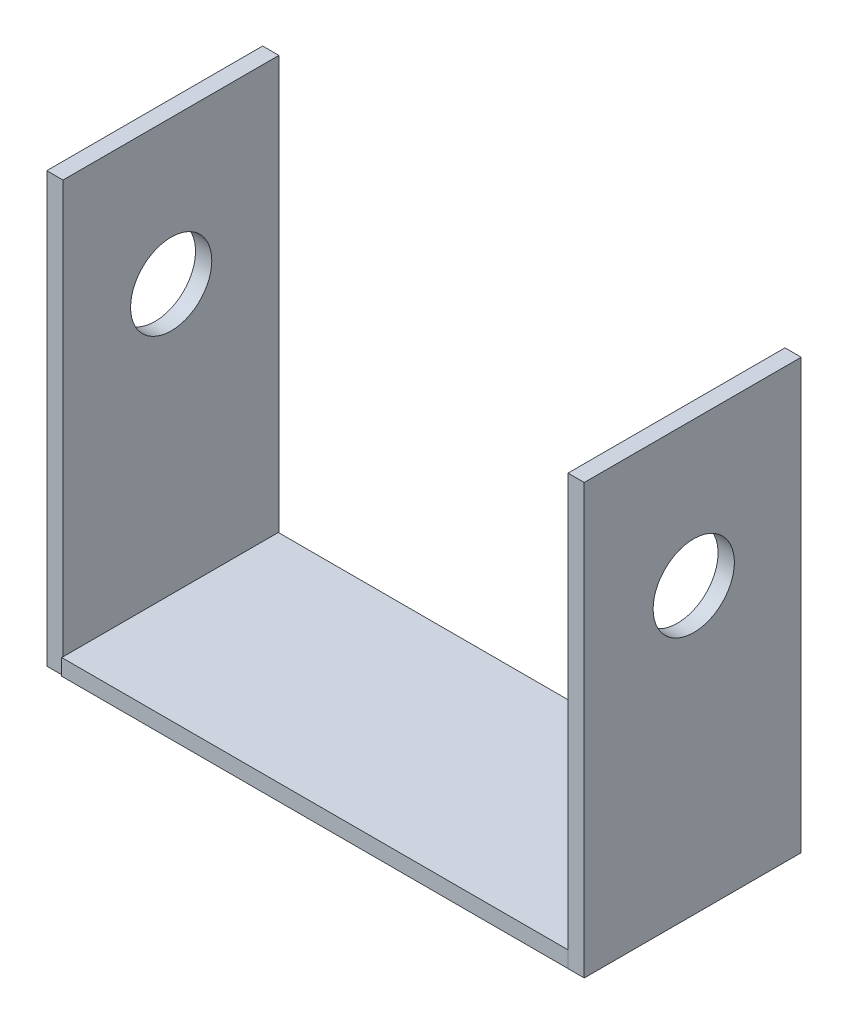
SolidWorks part; units mm, degrees
ref_plane "Front Plane" through (0, 0, 0) normal (0, 0, 1) x (1, 0, 0)
ref_plane "Top Plane" through (0, 0, 0) normal (0, 1, 0) x (1, 0, 0)
ref_plane "Right Plane" through (0, 0, 0) normal (1, 0, 0) x (0, 0, -1)
sketch "Sketch1" plane through (0, 0, 0) normal (0, 1, 0) x (1, 0, 0)
  line L1 (-23.7617, -10.16) -> (23.7617, -10.16)
  line L2 (-23.7617, -10.16) -> (-23.7617, 10.16)
  line L3 (-23.7617, 10.16) -> (23.7617, 10.16)
  line L4 (23.7617, -10.16) -> (23.7617, 10.16)
  line L5 (-23.7617, -10.16) -> (23.7617, 10.16) construction
  line L6 (-23.7617, 10.16) -> (23.7617, -10.16) construction
  point P0 (0, 0)
  dimension "D1" = 20.32
  dimension "D2" = 47.5234
extrude "Boss-Extrude1" add sketch "Sketch1" along normal blind 1.524
ref_plane "Plane1" through (-23.749, 0, 0) normal (1, 0, 0) x (0, 0, -1)
sketch "Sketch2" plane through (-23.749, 0, 0) normal (1, 0, 0) x (0, 0, -1)
  line L0 (10.2149, 0) -> (-10.0391, 0)
  line L1 (10.2149, 0) -> (10.2149, 40.259)
  line L2 (-10.0391, 0) -> (-10.0391, 40.259)
  line L3 (10.2149, 40.259) -> (-10.0391, 40.259)
  dimension "D1" = 20.254
  dimension "D2" = 40.259
extrude "Boss-Extrude2" add sketch "Sketch2" against normal blind 1.524
ref_plane "Plane2" through (23.749, 0, 0) normal (1, 0, 0) x (0, 0, -1)
sketch "Sketch3" plane through (23.749, 0, 0) normal (1, 0, 0) x (0, 0, -1)
  line L0 (-10.1629, 0) -> (10.1926, 0)
  line L1 (-10.1629, 0) -> (-10.1629, 40.259)
  line L2 (10.1926, 0) -> (10.1926, 40.259)
  line L3 (-10.1629, 40.259) -> (10.1926, 40.259)
  dimension "D1" = 20.3556
  dimension "D2" = 40.259
extrude "Boss-Extrude3" add sketch "Sketch3" along normal blind 1.524
ref_plane "Plane3" through (0, 40.259, 0) normal (0, 1, 0) x (1, 0, 0)
ref_point "Point1"
ref_axis "Axis1" through (-25.273, 44.6084, -0.0879) along (0, -1, 0)
sketch "Sketch5" plane through (-25.273, 0, 0) normal (-1, 0, 0) x (0, 0, 1)
  circle A0 centre (-0.1072, 26.7388) radius 3.81
extrude "Cut-Extrude1" cut sketch "Sketch5" against normal through all
